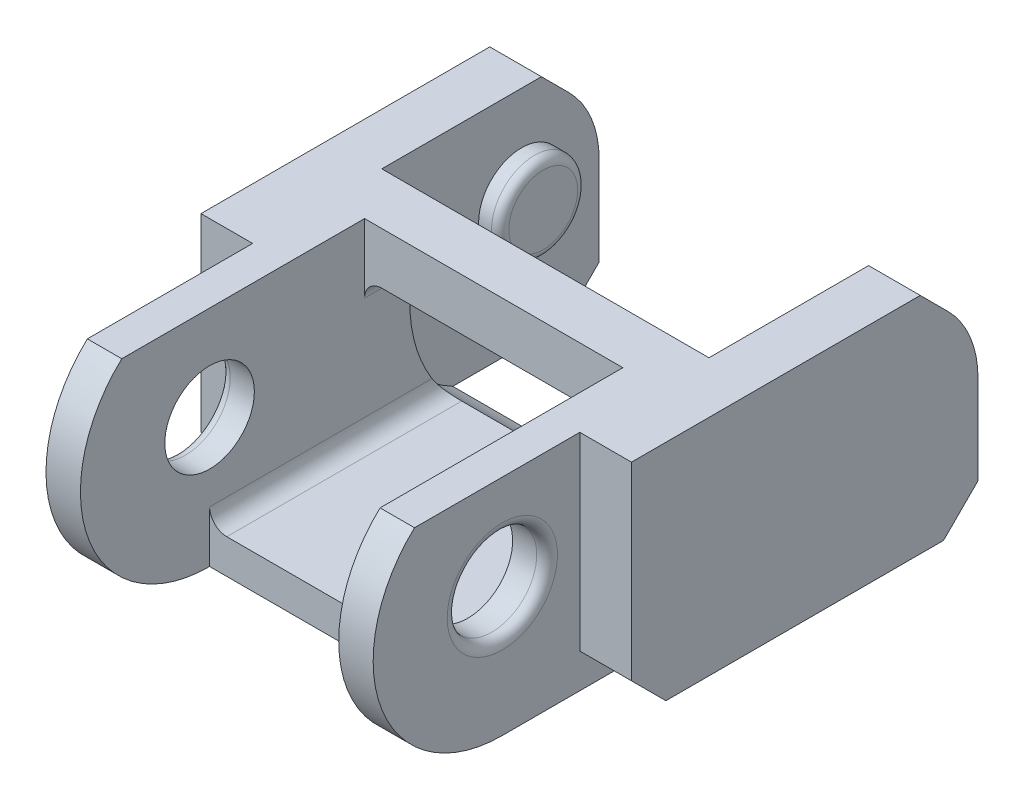
SolidWorks part; units mm, degrees
ref_plane "前基準面" through (0, 0, 0) normal (0, 0, 1) x (1, 0, 0)
ref_plane "上基準面" through (0, 0, 0) normal (0, 1, 0) x (1, 0, 0)
ref_plane "右基準面" through (0, 0, 0) normal (1, 0, 0) x (0, 0, -1)
sketch "草圖1" plane through (0, 0, 0) normal (0, 0, 1) x (1, 0, 0)
  line L1 (-1.8124, 12.3552) -> (23.1876, 12.3552)
  line L2 (-1.8124, 12.3552) -> (-1.8124, -0.6448)
  line L3 (-1.8124, -0.6448) -> (23.1876, -0.6448)
  line L4 (23.1876, 12.3552) -> (23.1876, -0.6448)
  line L5 (3.1876, 9.3552) -> (18.1876, 9.3552)
  line L6 (3.1876, 9.3552) -> (3.1876, 1.3552)
  line L7 (3.1876, 1.3552) -> (18.1876, 1.3552)
  line L8 (18.1876, 9.3552) -> (18.1876, 1.3552)
  dimension "D1" = 13
  dimension "D2" = 25
  dimension "D3" = 3
  dimension "D4" = 2
  dimension "D5" = 5
  dimension "D6" = 5
extrude "填料-伸長1" add sketch "草圖1" along normal blind 27
sketch "草圖2" plane through (0, 12.3552, 0) normal (0, 1, 0) x (1, 0, 0)
  line L0 (23.1876, 0) -> (-1.8124, 0) construction
  line L1 (1.1876, 0) -> (20.1876, 0)
  line L2 (1.1876, 0) -> (1.1876, -8)
  line L3 (1.1876, -8) -> (20.1876, -8)
  line L4 (20.1876, 0) -> (20.1876, -8)
  line L5 (-1.8124, -27) -> (-1.8124, 0) construction
  line L6 (23.1876, -27) -> (23.1876, 0) construction
  dimension "D1" = 3
  dimension "D2" = 3
  dimension "D3" = 8
extrude "除料-伸長1" cut sketch "草圖2" against normal blind 27
sketch "草圖3" plane through (20.1876, 0, 0) normal (-1, 0, 0) x (0, 0, 1)
  line L0 (0, -0.6448) -> (0, 12.3552) construction
  line L1 (8, 12.3552) -> (0, 12.3552) construction
  circle A0 centre (4.5, 6.8552) radius 2.5
  dimension "D2" = 5
  dimension "D1" = 4.5
  dimension "D3" = 5.5
extrude "填料-伸長2" add sketch "草圖3" along normal blind 2
sketch "草圖4" plane through (18.1876, 0, 0) normal (-1, 0, 0) x (0, 0, 1)
  circle A0 centre (4.5, 6.8552) radius 8.5
  circle A1 centre (4.5, 6.8552) radius 2.5
  dimension "D1" = 17
extrude "除料-伸長2" cut sketch "草圖4" against normal blind 2
sketch "草圖5" plane through (18.1876, 0, 0) normal (-1, 0, 0) x (0, 0, 1)
  circle A0 centre (4.5, 6.8552) radius 8.5
extrude "除料-伸長3" cut sketch "草圖5" along normal blind 17
sketch "草圖9" plane through (0, 12.3552, 0) normal (0, 1, 0) x (1, 0, 0)
  line L1 (20.1876, -10.9807) -> (1.1876, -10.9807)
  line L2 (20.1876, -10.9807) -> (20.1876, -11.7179)
  line L3 (20.1876, -11.7179) -> (1.1876, -11.7179)
  line L4 (1.1876, -10.9807) -> (1.1876, -11.7179)
extrude "除料-伸長7" cut sketch "草圖9" against normal blind 4
sketch "草圖10" plane through (0, 0, 11.7179) normal (0, 0, -1) x (-1, 0, 0)
  line L0 (-1.1876, 12.3552) -> (-20.1876, 12.3552) construction
  line L1 (-20.1876, 12.3552) -> (-1.1876, 12.3552)
  line L2 (-20.1876, 12.3552) -> (-20.1876, 9.3552)
  line L3 (-20.1876, 9.3552) -> (-1.1876, 9.3552)
  line L4 (-1.1876, 12.3552) -> (-1.1876, 9.3552)
  dimension "D1" = 19
  dimension "D2" = 3
extrude "除料-伸長8" cut sketch "草圖10" against normal up to vertex (0.9062 mm away) up to point (3.1876, 9.3552, 12.624)
sketch "草圖13" plane through (1.1876, 0, 0) normal (1, 0, 0) x (0, 0, -1)
  line L0 (0, 12.3552) -> (-12.624, 12.3552) construction
  line L1 (0, -0.6448) -> (0, 12.3552) construction
  circle A0 centre (-4.5, 6.8552) radius 2.5
  dimension "D3" = 5
  dimension "D1" = 5.5
  dimension "D2" = 4.5
extrude "填料-伸長4" add sketch "草圖13" along normal blind 2
sketch "草圖14" plane through (0, 12.3552, 0) normal (0, 1, 0) x (1, 0, 0)
  line L0 (20.1876, -12.624) -> (18.1876, -12.624) construction
  line L1 (-1.8124, -27) -> (1.1876, -27)
  line L2 (-1.8124, -27) -> (-1.8124, -19.624)
  line L3 (-1.8124, -19.624) -> (1.1876, -19.624)
  line L4 (1.1876, -27) -> (1.1876, -19.624)
  line L5 (23.1876, -27) -> (20.1876, -27)
  line L6 (23.1876, -27) -> (23.1876, -19.624)
  line L7 (23.1876, -19.624) -> (20.1876, -19.624)
  line L8 (20.1876, -27) -> (20.1876, -19.624)
  line L9 (23.1876, -27) -> (-1.8124, -27) construction
  line L10 (3.1876, -27) -> (18.1876, -27)
  line L11 (3.1876, -27) -> (3.1876, -19.624)
  line L12 (3.1876, -19.624) -> (18.1876, -19.624)
  line L13 (18.1876, -27) -> (18.1876, -19.624)
  dimension "D1" = 3
  dimension "D2" = 3
  dimension "D3" = 7
  dimension "D4" = 7
  dimension "D5" = 2
  dimension "D6" = 2
extrude "除料-伸長10" cut sketch "草圖14" against normal blind 30
sketch "草圖15" plane through (20.1876, 0, 0) normal (-1, 0, 0) x (0, 0, 1)
  line L0 (0, 9.002) -> (3.3532, 12.3552)
  line L1 (0, -0.6448) -> (0, 12.3552) construction
  line L2 (3.3532, 12.3552) -> (0, 12.3552)
  line L3 (0, 12.3552) -> (0, 9.002)
  circle A0 centre (4.5, 6.8552) radius 2.5 construction
  dimension "D1" = 45
  dimension "D2" = 4.7
extrude "除料-伸長11" cut sketch "草圖15" against normal through all both and the other way through all
fillet "圓角3" radius 6 2 edges at (-0.3124, 9.002, 0) (21.6876, 9.002, 0)
sketch "草圖18" plane through (20.1876, 0, 0) normal (1, 0, 0) x (0, 0, -1)
  line L0 (-19.624, 12.3552) -> (-27, 12.3552) construction
  line L1 (-19.624, -0.6448) -> (-19.624, 12.3552) construction
  circle A0 centre (-24.624, 6.8552) radius 7.5
  dimension "D3" = 15
  dimension "D1" = 5.5
  dimension "D2" = 5
sketch "草圖19" plane through (1.1876, 0, 0) normal (-1, 0, 0) x (0, 0, 1)
  line L0 (27, -0.6448) -> (19.624, -0.6448) construction
  line L1 (27, 12.3552) -> (24.624, 12.3552)
  line L2 (27, 12.3552) -> (27, -0.6448)
  line L3 (27, -0.6448) -> (24.624, -0.6448)
  line L4 (24.624, 12.3552) -> (24.624, -0.6448)
  line L5 (19.624, -0.6448) -> (19.624, 12.3552) construction
  dimension "D1" = 5
extrude "除料-伸長13" cut sketch "草圖19" against normal through all
extrude "填料-伸長5" add sketch "草圖18" against normal up to surface (2 mm away) up to face at (18.1876, 5.5789, 19.0466)
sketch "草圖20" plane through (1.1876, 0, 0) normal (-1, 0, 0) x (0, 0, 1)
  line L0 (24.624, 12.3552) -> (24.624, -0.6448) construction
  line L1 (24.624, 12.3552) -> (19.624, 12.3552) construction
  circle A0 centre (24.624, 6.8552) radius 7.5
  point P6 (22.124, 12.3552)
  dimension "D2" = 15
  dimension "D1" = 5.5
extrude "填料-伸長6" add sketch "草圖20" against normal up to surface (2 mm away) up to face at (3.1876, 5.5789, 19.0466)
sketch "草圖21" plane through (23.1876, 0, 0) normal (1, 0, 0) x (0, 0, -1)
  line L0 (-19.624, 12.3552) -> (-3.3532, 12.3552) construction
  line L1 (-14.2337, 12.3552) -> (-42.1498, 12.3552)
  line L2 (-14.2337, 12.3552) -> (-14.2337, 19.2087)
  line L3 (-14.2337, 19.2087) -> (-42.1498, 19.2087)
  line L4 (-42.1498, 12.3552) -> (-42.1498, 19.2087)
extrude "除料-伸長14" cut sketch "草圖21" against normal through all
sketch "草圖22" plane through (20.1876, 0, 0) normal (1, 0, 0) x (0, 0, -1)
  line L0 (-19.624, -0.6448) -> (-19.624, 12.3552) construction
  line L2 (-19.624, 12.3552) -> (-29.7231, 12.3552) construction
  circle A0 centre (-24.624, 6.8552) radius 2.6
  dimension "D3" = 5.2
  dimension "D1" = 5
  dimension "D2" = 5.5
extrude "除料-伸長15" cut sketch "草圖22" against normal through all both and the other way through all
fillet "圓角4" radius 0.6 1 edges at (20.1876, 6.8552, 27.224)
fillet "圓角5" radius 0.6 1 edges at (1.1876, 6.8552, 22.024)
fillet "圓角6" radius 1 2 edges at (3.1876, 9.3552, 16.124) (18.1876, 9.3552, 16.124)
fillet "圓角7" radius 0.5 3 edges at (3.4805, 9.0623, 19.624) (17.8947, 9.0623, 19.624) (10.6876, 9.3552, 19.624)
sketch "草圖23" plane through (3.1876, 0, 0) normal (1, 0, 0) x (0, 0, -1)
  circle A0 centre (-4.5, 6.8552) radius 2.5
extrude "除料-伸長16" cut sketch "草圖23" against normal blind 0.75
sketch "草圖25" plane through (18.1876, 0, 0) normal (-1, 0, 0) x (0, 0, 1)
  circle A0 centre (4.5, 6.8552) radius 2.5
extrude "除料-伸長17" cut sketch "草圖25" against normal blind 0.75
fillet "圓角8" radius 0.5 2 edges at (2.4376, 6.8552, 2) (18.9376, 6.8552, 7)
sketch "草圖27" plane through (0, 0, 19.624) normal (0, 0, 1) x (1, 0, 0)
  line L0 (18.1876, 12.3552) -> (3.1876, 12.3552)
  line L1 (18.1876, 12.3552) -> (18.1876, 8.1793)
  line L2 (3.1876, 12.3552) -> (3.1876, 8.1793)
  line L3 (18.1876, 8.1793) -> (3.1876, 8.1793)
extrude "除料-伸長18" cut sketch "草圖27" against normal blind 4
sketch "草圖28" plane through (0, 0, 19.624) normal (0, 0, 1) x (1, 0, 0)
  line L7 (18.1876, -0.6448) -> (3.1876, -0.6448)
  line L8 (18.1876, -0.6448) -> (18.1876, 1.3552)
  line L9 (3.1876, -0.6448) -> (3.1876, 1.3552)
  line L10 (18.1876, 1.3552) -> (3.1876, 1.3552)
  dimension "D1" = 2
extrude "填料-伸長8" add sketch "草圖28" along normal up to vertex (5 mm away) up to point (3.1876, -0.6448, 24.624)
fillet "圓角9" radius 1 2 edges at (18.1876, 1.3552, 17.8024) (3.1876, 1.3552, 17.8024)
sketch "草圖29" plane through (0, 0, 19.624) normal (0, 0, 1) x (1, 0, 0)
  line L1 (23.1876, -0.6448) -> (20.1876, -0.6448)
  line L2 (23.1876, -0.6448) -> (23.1876, 12.3552)
  line L3 (23.1876, 12.3552) -> (20.1876, 12.3552)
  line L4 (20.1876, -0.6448) -> (20.1876, 12.3552)
  line L5 (-1.8124, -0.6448) -> (1.1876, -0.6448)
  line L6 (-1.8124, -0.6448) -> (-1.8124, 12.3552)
  line L7 (-1.8124, 12.3552) -> (1.1876, 12.3552)
  line L8 (1.1876, -0.6448) -> (1.1876, 12.3552)
extrude "填料-伸長9" add sketch "草圖29" along normal blind 0.5
chamfer "導角1" distance 2 angle 45 4 edges at (-0.3124, -0.6448, 20.124) (21.6876, -0.6448, 20.124) (21.6876, -0.6448, 0) (-0.3124, -0.6448, 0)
